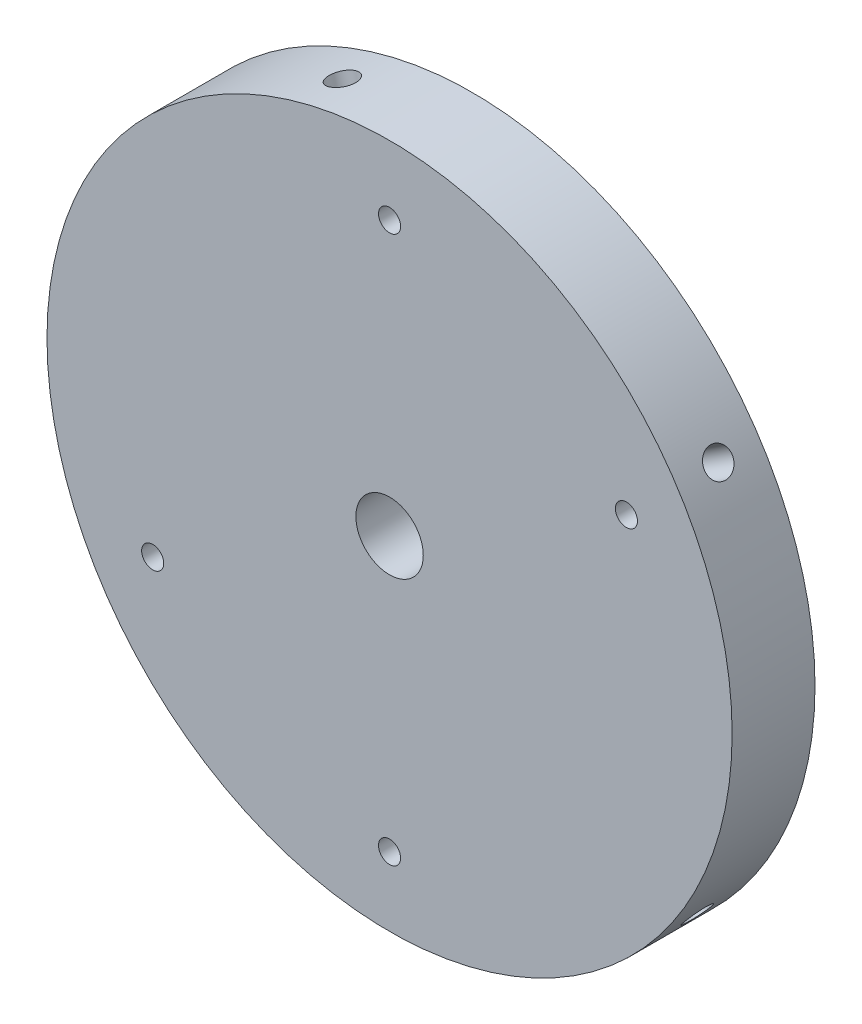
SolidWorks part; units mm, degrees
material "Polyetheretherketone (PEEK)"
ref_plane "Front Plane" through (0, 0, 0) normal (0, 0, 1) x (1, 0, 0)
ref_plane "Top Plane" through (0, 0, 0) normal (0, 1, 0) x (1, 0, 0)
ref_plane "Right Plane" through (0, 0, 0) normal (1, 0, 0) x (0, 0, -1)
sketch "Sketch1" plane through (0, 0, 0) normal (0, 0, 1) x (1, 0, 0)
  circle A0 centre (0, 0) radius 62
  dimension "D1" = 124
extrude "Boss-Extrude1" add sketch "Sketch1" along normal blind 15 contours A0
sketch "Sketch2" plane through (0, 0, 15) normal (0, 0, 1) x (1, 0, 0)
  circle A0 centre (0, 49.5) radius 2
  dimension "D1" = 4
  dimension "D2" = 49.5
extrude "Cut-Extrude1" cut sketch "Sketch2" against normal blind 15
pattern_circular "CirPattern1" count 2 every 60 about axis through (0, 0, 15) along (0, 0, -1) of "Cut-Extrude1"
pattern_circular "CirPattern2" count 2 every 180 about axis through (0, 0, 15) along (0, 0, -1) of "CirPattern1", "Cut-Extrude1"
sketch "Sketch3" plane through (0, 0, 15) normal (0, 0, 1) x (1, 0, 0)
  circle A0 centre (0, 0) radius 6.1
  dimension "D1" = 12.2
extrude "Cut-Extrude2" cut sketch "Sketch3" against normal blind 15
ref_plane "Plane1" through (62, 0, 0) normal (1, 0, 0) x (0, 0, -1)
sketch "Sketch5" plane through (0, 0, 0) normal (0, 0, -1) x (-1, 0, 0)
  line L0 (0, 0) -> (-51.9976, 33.7676)
  line L1 (0, 0) -> (-62, 0)
  line L2 (-62, 8.25) -> (-62, -8.25) construction
  circle A0 centre (0, 0) radius 62 construction
  dimension "D1" = 33
sketch "Sketch6" plane through (0, 0, 0) normal (1, 0, 0) x (0, 0, -1)
  line L0 (0, 0) -> (-29.3997, 0)
ref_plane "Plane3" through (0, 0, 0) normal (0.8387, 0.5446, 0) x (0, 0, -1)
ref_plane "Plane4" through (51.9976, 33.7676, 0) normal (0.8387, 0.5446, 0) x (0, 0, -1)
sketch "Sketch4" plane through (51.9976, 33.7676, 0) normal (-0.8387, -0.5446, 0) x (0, 0, -1)
  circle A0 centre (-7.5, 0) radius 2.5
  dimension "D1" = 5
  dimension "D2" = 7.5
extrude "Cut-Extrude4" cut sketch "Sketch4" along normal blind 10 contours A0
pattern_circular "CirPattern5" count 5 every 72 about axis through (0, 0, 0) along (0, 0, 1) of "Cut-Extrude4"
